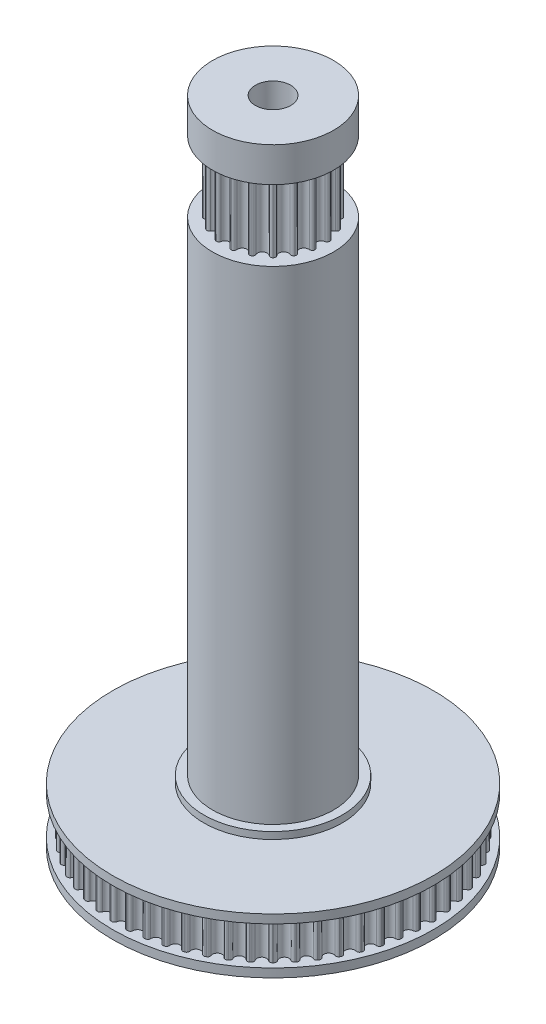
SolidWorks part; units mm, degrees
ref_plane "Front Plane" through (0, 0, 0) normal (0, 0, 1) x (1, 0, 0)
ref_plane "Top Plane" through (0, 0, 0) normal (0, 1, 0) x (1, 0, 0)
ref_plane "Right Plane" through (0, 0, 0) normal (1, 0, 0) x (0, 0, -1)
sketch "PulleyOffsets" plane through (0, 0, 0) normal (1, 0, 0) x (0, 0, -1)
  line L0 (50.8, 0) -> (-50.8, 0) construction
  line L1 (50.8, 101.6) -> (-50.8, 101.6) construction
  line L2 (0, 0) -> (0, 101.6) construction
  point P7 (0, 0)
  dimension "D1" = 101.6
ref_axis "Axis1" through (0, 34.9332, 0) along (0, -1, 0)
ref_plane "Big Pulley Plane" through (0, 0, 0) normal (0, 1, 0) x (1, 0, 0)
ref_plane "Small Pulley Plane" through (0, 101.6, 0) normal (0, 1, 0) x (1, 0, 0)
sketch "Sketch1" plane through (0, 0, 0) normal (0, 1, 0) x (1, 0, 0)
  line L0 (0, 0) -> (0, 28.2667) construction
  line L1 (0, 0) -> (2.9202, 27.7837) construction
  circle A0 centre (0, 0) radius 28.2667 construction
  circle A1 centre (0, 0) radius 27.0467 construction
  circle A2 centre (0, 27.9367) radius 0.89 construction
  circle A5 centre (2.9202, 27.7837) radius 0.89 construction
  arc A6 (0, 27.0467) -> (0.8804, 27.8061) centre (0, 27.9367) ccw
  arc A7 (0.8804, 27.8061) -> (1.3997, 28.2321) centre (1.3749, 27.7327) cw
  arc A8 (1.559, 28.2237) -> (2.031, 27.7458) centre (1.5314, 27.7245) cw
  arc A9 (2.8272, 26.8986) -> (2.031, 27.7458) centre (2.9202, 27.7837) cw
  arc A10 (1.3997, 28.2321) -> (1.559, 28.2237) centre (0, 0) cw
  arc A11 (0, 27.0467) -> (2.8272, 26.8986) centre (0, 0) ccw
  dimension "D1" = 56.5335
  dimension "D3" = 1.78
  dimension "D4" = 0.5
  dimension "D2" = 1.22
  dimension "D5" = 6
extrude "Boss-Extrude1" add sketch "Sketch1" along normal mid plane 7.112 contours A6 A11 A9 A8 A7 region at (0.001, 0, -0.0192)
pattern_circular "CirPattern1" count 60 over 360 about axis through (0, 34.9332, 0) along (0, -1, 0) of "Boss-Extrude1"
sketch "Sketch2" plane through (0, 0, 0) normal (1, 0, 0) x (0, 0, -1)
  line L10 (0, 3.5) -> (29.4415, 3.5) construction
  line L11 (0, 3.5) -> (0, 5.0875) construction
  line L12 (0, 5.0875) -> (29.4415, 5.0875) construction
  line L15 (29.4415, 3.5) -> (29.4415, 5.0875) construction
  line L20 (0, 34.9332) -> (0, -6.9932) construction
  line L22 (29.4415, 5.0875) -> (0, 5.0875)
  line L23 (29.4415, 5.0875) -> (29.4415, 3.5)
  line L24 (29.4415, 3.5) -> (0, 3.5)
  line L25 (0, 5.0875) -> (0, 3.5)
  dimension "D1" = 1.5875
  dimension "D2" = 29.4415
  dimension "D3" = 3.5
revolve "Revolve3" add sketch "Sketch2" angle 360 about axis through (0, 34.9332, 0) along (0, -1, 0) region at (0, 4.2937, -14.7207)
mirror "Mirror1" about plane through (0, 0, 0) normal (0, 1, 0) of "Revolve3"
sketch "Sketch3" plane through (0, 0, 0) normal (0, 1, 0) x (1, 0, 0)
  circle A0 centre (0, 0) radius 22.225
  dimension "D1" = 44.45
extrude "Cut-Extrude1" [suppressed] cut sketch "Sketch3" against normal through all both and the other way through all
sketch "Sketch6" plane through (0, 0, 0) normal (0, 1, 0) x (1, 0, 0)
  line L0 (0, 0) -> (0, 9.1676) construction
  line L1 (0, 0) -> (2.731, 8.405) construction
  circle A0 centre (0, 0) radius 9.1676 construction
  circle A1 centre (0, 0) radius 7.9476 construction
  circle A2 centre (0, 8.8376) radius 0.89 construction
  circle A5 centre (2.731, 8.405) radius 0.89 construction
  arc A6 (0, 7.9476) -> (0.8721, 8.6598) centre (0, 8.8376) ccw
  arc A7 (0.8721, 8.6598) -> (1.4405, 9.0537) centre (1.362, 8.5599) cw
  arc A8 (1.4277, 9.0557) -> (1.8466, 8.5054) centre (1.3498, 8.5618) cw
  arc A9 (2.4559, 7.5586) -> (1.8466, 8.5054) centre (2.731, 8.405) cw
  arc A10 (1.4405, 9.0537) -> (1.4277, 9.0557) centre (0, 0) cw construction
  arc A11 (0, 7.9476) -> (2.4559, 7.5586) centre (0, 0) ccw
  arc A12 (1.4405, 9.0537) -> (1.4277, 9.0557) centre (0, 0) cw
  dimension "D3" = 1.78
  dimension "D4" = 0.5
  dimension "D2" = 1.22
  dimension "D1" = 18.3352
  dimension "D5" = 18
extrude "Boss-Extrude2" add sketch "Sketch6" along normal mid plane 13 from surface contours A6 A11 A9 A8 A7 region at (0.0089, 0, -0.0564) starting at plane "Small Pulley Plane"
pattern_circular "CirPattern2" count 20 over 360 about axis through (0, 34.9332, 0) along (0, -1, 0) of "Boss-Extrude2"
sketch "Sketch4" plane through (0, 0, 0) normal (0, 0, 1) x (1, 0, 0)
  line L0 (12.7, 5.0875) -> (-12.7, 5.0875) construction
  line L1 (29.4415, 5.0875) -> (-29.4415, 5.0875) construction
  line L2 (-12.7, 5.0875) -> (-12.7, 6.3575)
  line L3 (-12.7, 6.3575) -> (-11.1125, 6.3575)
  line L4 (-11.1125, 6.3575) -> (-11.1125, 95.1)
  line L5 (0, 0) -> (0, 114.45) construction
  line L6 (11.1125, 6.3575) -> (11.1125, 95.1) construction
  line L7 (12.7, 6.3575) -> (11.1125, 6.3575) construction
  line L8 (12.7, 5.0875) -> (12.7, 6.3575) construction
  line L9 (-11.1125, 95.1) -> (11.1125, 95.1) construction
  line L10 (-12.7, 5.0875) -> (0, 5.0875)
  line L11 (0, 5.0875) -> (0, 95.1)
  line L12 (0, 95.1) -> (-11.1125, 95.1)
  line L13 (1.841, 95.1) -> (3.5054, 95.1) construction
  line L14 (0.8721, 108.1) -> (-0.8721, 108.1) construction
  line L15 (-11.1125, 114.45) -> (0, 114.45)
  line L16 (-11.1125, 114.45) -> (-11.1125, 108.1)
  line L17 (-11.1125, 108.1) -> (0, 108.1)
  line L18 (0, 114.45) -> (0, 108.1)
  line L19 (-11.1125, 95.1) -> (-11.1125, 108.1) construction
  point P14 (0, 5.0875)
  dimension "D1" = 1.27
  dimension "D2" = 25.4
  dimension "D3" = 22.225
  dimension "D4" = 6.35
revolve "Revolve4" add sketch "Sketch4" angle 360 about L11
sketch "Sketch7" plane through (0, 114.45, 0) normal (0, 1, 0) x (1, 0, 0)
  circle A0 centre (0, 0) radius 3.2385
  dimension "D1" = 6.477
extrude "Cut-Extrude2" cut sketch "Sketch7" against normal through all both and the other way through all
equation "\"TEETH_NUM\"= 60"
equation "\"TOOTH_PITCH\"= 3mm"
equation "\"PITCH_LINE_OFFSET\"= .015in"
equation "\"DIAMETER_PER_GROOVE\"= \"OUTSIDE_DIAMETER\" / \"TEETH_NUM\" * 1in"
equation "\"PITCH_DIAMETER\"= ( ( \"TEETH_NUM\" * 3 - 1.31 ) / 3.1415 + .415 ) * 1mm"
equation "\"OUTSIDE_DIAMETER\"= \"PITCH_DIAMETER\" - \"PITCH_LINE_OFFSET\" * 2"
equation "\"D1@Sketch1\"=\"OUTSIDE_DIAMETER\""
equation "\"TOOTH_HEIGHT\"= 1.22mm"
equation "\"D2@Sketch1\"=\"TOOTH_HEIGHT\""
equation "\"TOOTH_DIAMETER\"= 1.78mm"
equation "\"INTERNAL_RADIUS\"= .5mm"
equation "\"D3@Sketch1\"=\"TOOTH_DIAMETER\""
equation "\"D5@Sketch1\"=360 / \"TEETH_NUM\""
equation "\"D4@Sketch1\"=\"INTERNAL_RADIUS\""
equation "\"D1@CirPattern1\"=\"TEETH_NUM\""
equation "\"BELT_GAP\"= 7mm"
equation "\"D2@Sketch2\"=\"PITCH_DIAMETER\"/2+1/32"
equation "\"D3@Sketch2\"=\"BELT_GAP\"/2"
equation "\"2_TEETH_NUM\"= 20"
equation "\"2_PITCH_DIAMETER\"= ( ( \"2_TEETH_NUM\" * 3 - 1.31 ) / 3.1415 + .415 ) * 1mm"
equation "\"2_OUTSIDE_DIAMETER\"= \"2_PITCH_DIAMETER\" - \"PITCH_LINE_OFFSET\" * 2"
equation "\"2_DIAMETER_PER_GROOVE\"= \"2_OUTSIDE_DIAMETER\" / \"2_TEETH_NUM\" * 1in"
equation "\"D5@Sketch6\"=360/\"2_TEETH_NUM\""
equation "\"D1@Sketch6\"=\"2_OUTSIDE_DIAMETER\""
equation "\"D2@Sketch6\"=\"TOOTH_HEIGHT\""
equation "\"D3@Sketch6\"=\"TOOTH_DIAMETER\""
equation "\"D4@Sketch6\"=\"INTERNAL_RADIUS\""
equation "\"2_BELT_GAP\"= 13mm"
equation "\"D1@CirPattern2\"=\"2_TEETH_NUM\""
equation "\"D1@Boss-Extrude2\"=\"2_BELT_GAP\""
equation "\"Pulley_OffSets\"= 4"
equation "\"D1@PulleyOffsets\" = \"Pulley_OffSets\""
